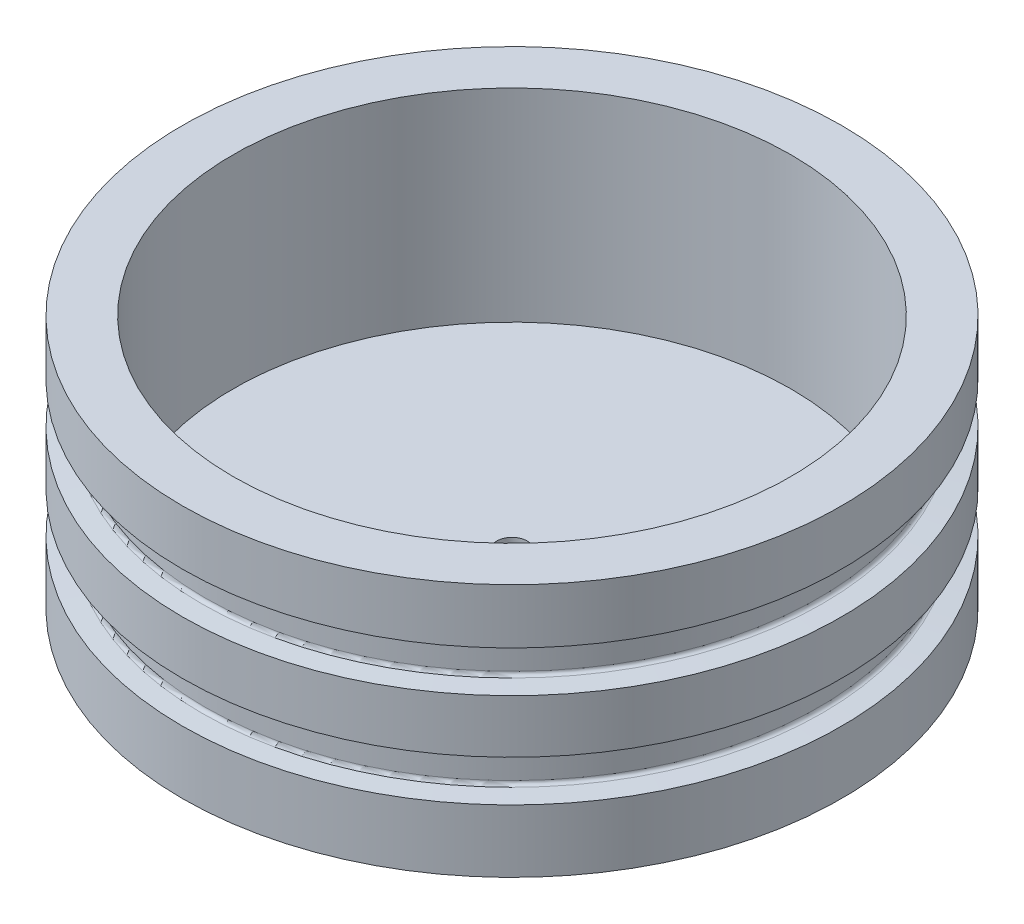
SolidWorks part; units mm, degrees
material "1060 Alloy"
ref_plane "Front Plane" through (0, 0, 0) normal (0, 0, 1) x (1, 0, 0)
ref_plane "Top Plane" through (0, 0, 0) normal (0, 1, 0) x (1, 0, 0)
ref_plane "Right Plane" through (0, 0, 0) normal (1, 0, 0) x (0, 0, -1)
sketch "Sketch1" plane through (0, 0, 0) normal (0, 0, 1) x (1, 0, 0)
  line L0 (0, 0) -> (0, 25.4) construction
  line L1 (-41.275, 0) -> (-41.275, 31.75)
  line L2 (-41.275, 0) -> (-6.35, 0)
  line L3 (-1.9133, 0) -> (-1.9133, 6.35)
  line L4 (-1.9133, 6.35) -> (-34.925, 6.35)
  line L5 (-34.925, 6.35) -> (-34.925, 31.75)
  line L6 (-34.925, 31.75) -> (-41.275, 31.75)
  line L7 (-1.9133, 0) -> (-1.9133, -12.7)
  line L8 (-1.9133, -12.7) -> (-6.35, -12.7)
  line L9 (-6.35, -12.7) -> (-6.35, 0)
  dimension "D1" = 1.9133
  dimension "D2" = 34.925
  dimension "D3" = 31.75
  dimension "D4" = 6.35
  dimension "D5" = 6.35
  dimension "D6" = 12.7
  dimension "D7" = 6.35
revolve "Revolve1" add sketch "Sketch1" angle 360 about L0
ref_plane "Plane1" through (0, 0, 0) normal (-1, 0, 0) x (0, 0, -1)
ref_plane "Plane2" through (0, 0, 0) normal (-1, 0, 0) x (0, 0, -1)
ref_plane "Plane3" through (0, 0, 0) normal (-1, 0, 0) x (0, 0, -1)
ref_plane "Plane4" through (0, 0, 0) normal (-1, 0, 0) x (0, 0, -1)
ref_plane "Plane5" through (0, 0, 0) normal (-1, 0, 0) x (0, 0, -1)
ref_plane "Plane6" through (0, 0, 0) normal (-1, 0, 0) x (0, 0, -1)
sketch "Sketch13" plane through (0, 0, 0) normal (-1, 0, 0) x (0, 0, -1)
  line L0 (38.8614, -19.9233) -> (41.3639, -19.7043)
  line L1 (41.3639, -19.7043) -> (41.3639, -24.892)
  line L2 (41.3639, -24.892) -> (38.8614, -24.6731)
  line L3 (38.4556, -24.2302) -> (38.4556, -20.3661)
  line L4 (0, 50) -> (0, -50) construction
  line L6 (-41.275, -31.75) -> (41.275, -31.75) construction
  arc A0 (38.8614, -24.6731) -> (38.4556, -24.2302) centre (38.9001, -24.2302) cw
  arc A1 (38.4556, -20.3661) -> (38.8614, -19.9233) centre (38.9001, -20.3661) cw
  dimension "D1" = 6.858
revolve "Groove for AS 568-234, O-Ring1" cut sketch "Sketch13"
pattern_linear "LPattern1" count 2 spacing 11.8533 along (0, -1, 0) of "Groove for AS 568-234, O-Ring1"
